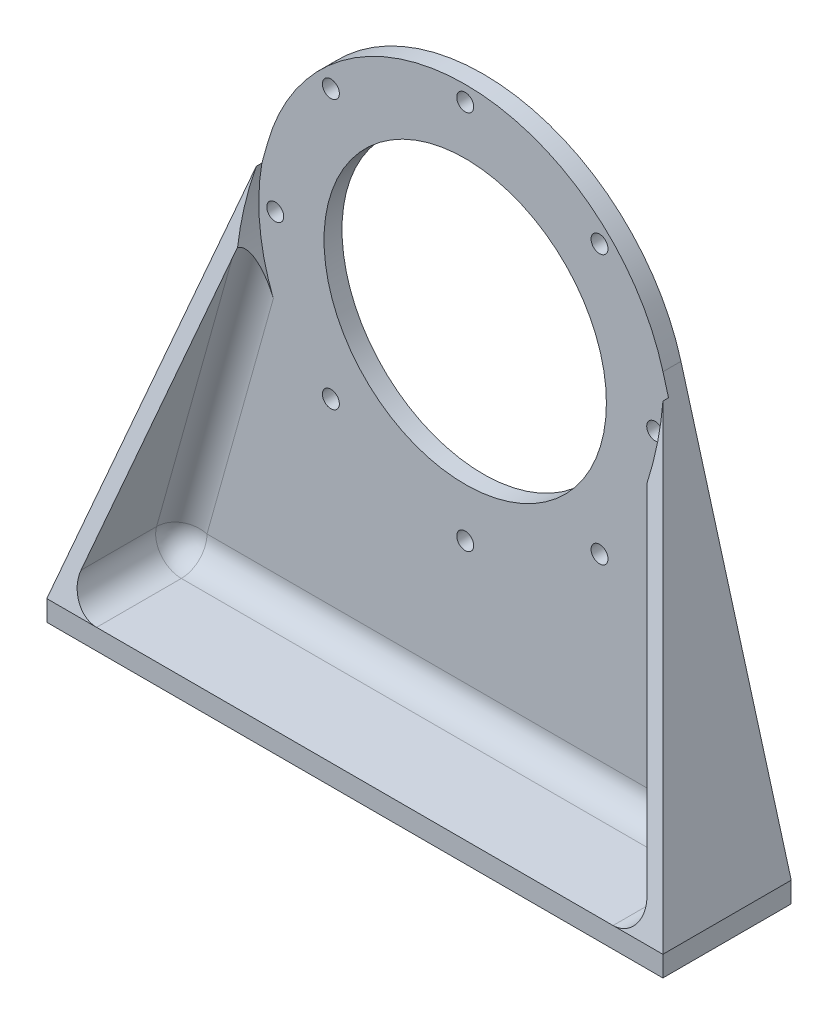
SolidWorks part; units mm, degrees
ref_plane "前视基准面" through (0, 0, 0) normal (0, 0, 1) x (1, 0, 0)
ref_plane "上视基准面" through (0, 0, 0) normal (0, 1, 0) x (1, 0, 0)
ref_plane "右视基准面" through (0, 0, 0) normal (1, 0, 0) x (0, 0, -1)
sketch "草图1" plane through (0, 0, 0) normal (0, 0, 1) x (1, 0, 0)
  line L0 (0, -70) -> (60, -70)
  line L1 (0, -70) -> (-60, -70)
  line L2 (-60, -66) -> (60, -66)
  line L3 (60, -70) -> (60, -66)
  line L4 (-60, -70) -> (-60, -66)
  line L5 (-60, -66) -> (-38.521, 10.7766)
  line L6 (60, -66) -> (38.521, 10.7766)
  line L7 (-56.8848, -66) -> (-35.6319, 9.9684)
  line L8 (56.8848, -66) -> (35.6319, 9.9684)
  line L9 (-57.1109, -66.8082) -> (-35.6319, 9.9684) construction
  line L14 (57.1109, -66.8082) -> (35.6319, 9.9684) construction
  arc A0 (38.521, 10.7766) -> (-38.521, 10.7766) centre (0, 0) ccw
  circle A1 centre (0, 0) radius 27.5
  circle A2 centre (0, 0) radius 37 construction
  circle A3 centre (0, 37) radius 1.65
  circle A4 centre (26.163, 26.163) radius 1.65
  circle A5 centre (37, 0) radius 1.65
  circle A6 centre (26.163, -26.163) radius 1.65
  circle A7 centre (0, -37) radius 1.65
  circle A8 centre (-26.163, -26.163) radius 1.65
  circle A9 centre (-37, 0) radius 1.65
  circle A10 centre (-26.163, 26.163) radius 1.65
  arc A11 (35.6319, 9.9684) -> (-35.6319, 9.9684) centre (0, 0) ccw
  point P29 (0, 0)
  dimension "D1" = 80
  dimension "D2" = 3.3
  dimension "D4" = 3
  dimension "D3" = 8
extrude "凸台-拉伸3" add sketch "草图1" along normal blind 25 contours A11 L8 A5 L2 L6 A0 L5 L7 A9 A10 A3 A4 | L4 L1 L0 L3 L2 region at (0, -68, 0) region at (58.4424, -64.3989, 0)
extrude "凸台-拉伸4" add sketch "草图1<5>" along normal blind 3.5 contours L8 A11 A4 A3 A10 L7 A9 L2 A5 A8 A7 A6 A1 region at (0, -31.0314, 0)
sketch "草图1<5>" plane through (0, 0, 0) normal (0, 0, 1) x (1, 0, 0) same geometry as "草图1"
sketch "草图2" plane through (0, 0, 0) normal (1, 0, 0) x (0, 0, -1)
  line L0 (-25, -66) -> (-3.5, 10.7766)
  line L1 (-25, 10.7766) -> (0, 10.7766) construction
  line L2 (0, 10.7766) -> (0, 40) construction
  line L3 (-3.5, 10.7766) -> (-3.5, 62.872)
  line L4 (-3.5, 62.872) -> (-39.2939, 54.5747)
  line L5 (-39.2939, 54.5747) -> (-52.2717, -41.589)
  line L6 (-52.2717, -41.589) -> (-25, -66)
  dimension "D1" = 3.5
extrude "切除-拉伸1" cut sketch "草图2" against normal blind 90 and the other way blind 116
sketch "草图3" plane through (0, 0, 3.5) normal (0, 0, 1) x (1, 0, 0)
  circle A0 centre (0, 0) radius 40.2
  dimension "D1" = 80.4
extrude "切除-拉伸2" cut sketch "草图3" along normal blind 90 from surface starting at face at (27.813, 26.163, 3.5)
fillet "圆角1" radius 5 5 edges at (-56.8848, -66, 14.25) (56.8848, -66, 14.25) (0, -66, 3.5) (-48.3756, -35.584, 3.5) (48.3756, -35.584, 3.5)
